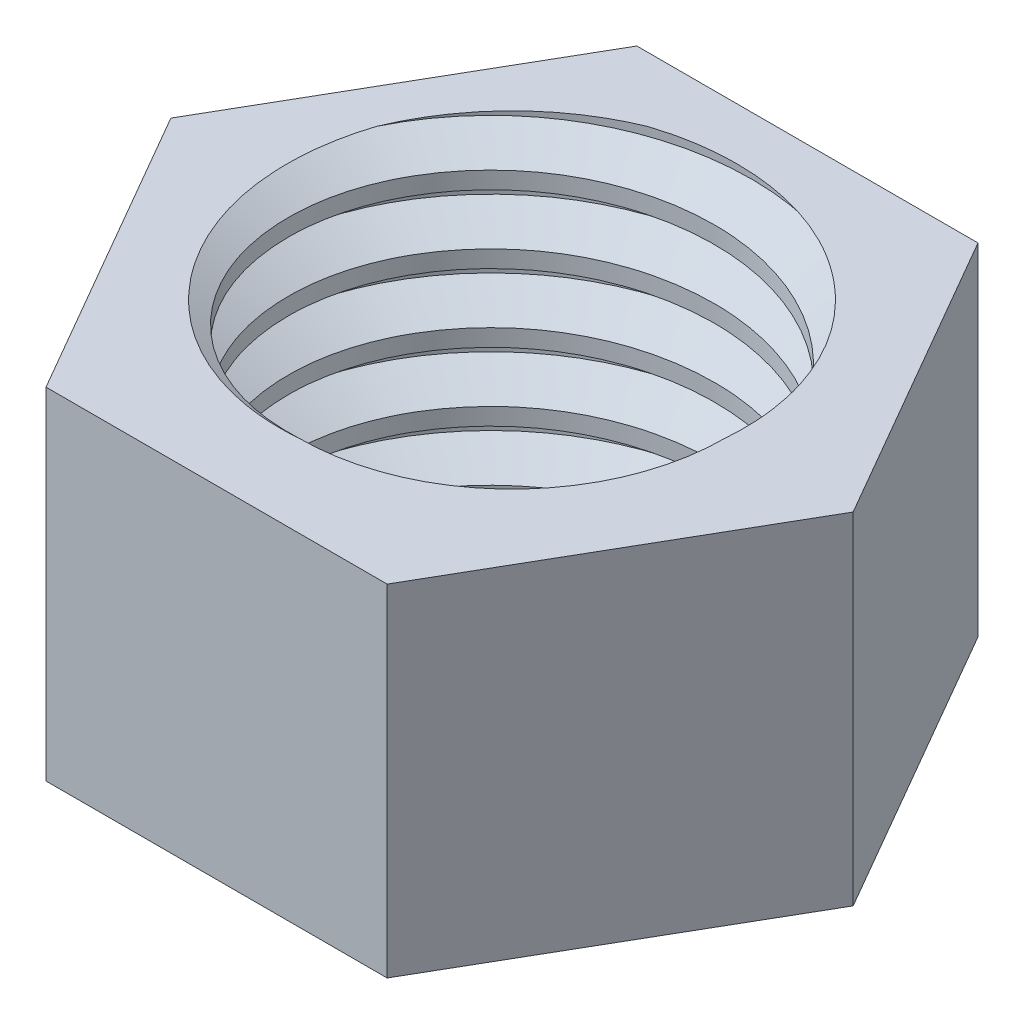
SolidWorks part; units mm, degrees
ref_plane "前视基准面" through (0, 0, 0) normal (0, 0, 1) x (1, 0, 0)
ref_plane "上视基准面" through (0, 0, 0) normal (0, 1, 0) x (1, 0, 0)
ref_plane "右视基准面" through (0, 0, 0) normal (1, 0, 0) x (0, 0, -1)
other "Configuration Table"
sketch "草图1" plane through (0, 0, 0) normal (0, 1, 0) x (1, 0, 0)
  line L2 (4, 0) -> (2, 3.4641)
  line L3 (2, 3.4641) -> (-2, 3.4641)
  line L4 (-2, 3.4641) -> (-4, 0)
  line L5 (-4, 0) -> (-2, -3.4641)
  line L6 (-2, -3.4641) -> (2, -3.4641)
  line L7 (2, -3.4641) -> (4, 0)
  circle A0 centre (0, 0) radius 3.4641 construction
  dimension "D1" = 8
extrude "凸台-拉伸1" add sketch "草图1" along normal blind 4
sketch "草图4" plane through (0, 4, 0) normal (0, 1, 0) x (1, 0, 0)
  circle A0 centre (0, 0) radius 2.5
extrude "切除-拉伸2" cut sketch "草图4" against normal through all
thread "螺纹线1" pitch 0.8 method cut profile "螺纹线轮廓1" start angle 0, offset 2, length 8, pitch 0.8, diameter 5
ref_plane "基准面1" through (-2.5, 6, 0) normal (0, 0, 1) x (-1, 0, 0)
sketch "螺纹线轮廓1" plane through (-2.5, 6, 0) normal (0, 0, 1) x (-1, 0, 0)
  line L0 (0, 0) -> (0, 0.8) construction
  line L1 (0, 0) -> (0.433, 0.25)
  line L2 (0.433, 0.25) -> (0.433, 0.35)
  line L3 (0.433, 0.35) -> (0, 0.6)
  line L4 (0.433, 0.3) -> (0, 0.3) construction
  line L11 (0, 0) -> (0, 0.6)
  point P2 (0, 0)
  dimension "Pitch" = 0.8
  dimension "Profile_Angle" = 60
  dimension "Profile_Land" = 0.1
  dimension "Profile_Height" = 0.433
